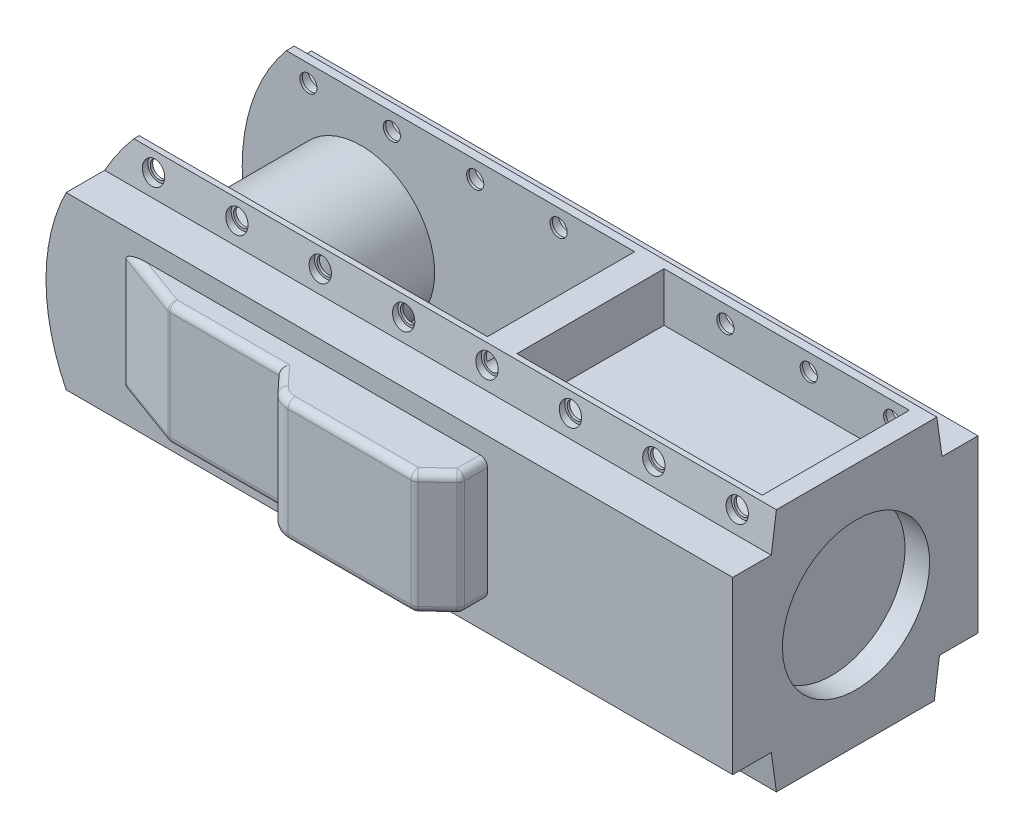
SolidWorks part; units mm, degrees
note: The reader was unsure of these and kept them because the rebuilt part matched: shared geometry of "Sketch8<3>".
ref_plane "Front Plane" through (0, 0, 0) normal (0, 0, 1) x (1, 0, 0)
ref_plane "Top Plane" through (0, 0, 0) normal (0, 1, 0) x (1, 0, 0)
ref_plane "Right Plane" through (0, 0, 0) normal (1, 0, 0) x (0, 0, -1)
sketch "Sketch1" plane through (0, 0, 0) normal (0, 0, 1) x (1, 0, 0)
sketch_block_instance "Block5-1"
sketch_block "Block5" parameters "D1"=43.5311
sketch "Sketch2" plane through (0, 0, 0) normal (0, 0, 1) x (1, 0, 0)
  line L0 (130.4545, 46.606) -> (113.6122, 46.606) construction
  line L1 (113.6075, 146.2711) -> (-166.3925, 146.2711)
  line L2 (113.6075, 146.2711) -> (113.6075, 46.606)
  line L3 (113.6075, 46.606) -> (-166.3925, 46.606)
  line L4 (-166.3925, 146.2711) -> (-166.3925, 46.606)
  dimension "D1" = 280
extrude "Boss-Extrude1" add sketch "Sketch2" along normal mid plane 100
sketch "Sketch3" plane through (0, 0, 50) normal (0, 0, 1) x (1, 0, 0)
  line L0 (113.6075, 146.2711) -> (-166.3925, 146.2711) construction
  line L1 (-166.3925, 46.606) -> (113.6075, 46.606) construction
  line L2 (-148.3925, 146.2711) -> (-166.3925, 146.2711)
  line L3 (-166.3925, 146.2711) -> (-166.3925, 46.606)
  line L4 (-166.3925, 46.606) -> (-148.3925, 46.606)
  arc A0 (-148.3925, 146.2711) -> (-148.3925, 46.606) centre (-88.4125, 96.4386) ccw
  line M4 (113.6075, 146.2711) -> (-166.3925, 146.2711)
  line M5 (-166.3925, 146.2711) -> (-166.3925, 46.606)
  line M6 (-166.3925, 46.606) -> (113.6075, 46.606)
  dimension "D1" = 18
  dimension "D2" = 18
extrude "Cut-Extrude1" cut sketch "Sketch3" against normal through all contours A0 M4 M5 | A0 L3 M6
sketch "Sketch4" plane through (0, 146.2711, 0) normal (0, 1, 0) x (1, 0, 0)
  line L0 (113.6075, 0) -> (-117.9126, 0) construction
  line L1 (113.6075, -50) -> (113.6075, 50) construction
  line L2 (-148.3925, 50) -> (-148.3925, -50) construction
  line L3 (-290.3925, 30) -> (-6.3925, 30)
  line L4 (-290.3925, 30) -> (-290.3925, -30)
  line L5 (-290.3925, -30) -> (-6.3925, -30)
  line L6 (-6.3925, 30) -> (-6.3925, -30)
  line L7 (-290.3925, 30) -> (-6.3925, -30) construction
  line L8 (-290.3925, -30) -> (-6.3925, 30) construction
  point P5 (-148.3925, 0)
  dimension "D2" = 120
  dimension "D3" = 60
extrude "Cut-Extrude2" cut sketch "Sketch4" against normal through all
sketch "Sketch6" plane through (113.6075, 0, 0) normal (1, 0, 0) x (0, 0, -1)
  line L1 (-50, 146.2711) -> (-35, 146.2711)
  line L2 (-50, 146.2711) -> (-50, 131.2711)
  line L3 (-50, 131.2711) -> (-35, 131.2711)
  line L4 (-35, 146.2711) -> (-35, 131.2711)
  line L5 (50, 146.2711) -> (36.0483, 146.2711)
  line L6 (50, 146.2711) -> (50, 131.2711)
  line L7 (50, 131.2711) -> (36.0483, 131.2711)
  line L8 (36.0483, 146.2711) -> (36.0483, 131.2711)
  line L9 (-50, 46.606) -> (-35, 46.606)
  line L10 (-50, 46.606) -> (-50, 61.606)
  line L11 (-50, 61.606) -> (-35, 61.606)
  line L12 (-35, 46.606) -> (-35, 61.606)
  line L13 (50, 46.606) -> (35, 46.606)
  line L14 (50, 46.606) -> (50, 61.606)
  line L15 (50, 61.606) -> (35, 61.606)
  line L16 (35, 46.606) -> (35, 61.606)
  dimension "D1" = 15
  dimension "D2" = 15
  dimension "D3" = 15
  dimension "D4" = 13.9517
  dimension "D5" = 15
  dimension "D6" = 15
  dimension "D7" = 15
  dimension "D8" = 15
extrude "Cut-Extrude3" cut sketch "Sketch6" against normal through all
sketch "Sketch7" plane through (0, 0, 0) normal (0, 0, 1) x (1, 0, 0)
  circle A0 centre (-117.9126, 98.0301) radius 30
  dimension "D1" = 60
extrude "Boss-Extrude2" add sketch "Sketch7" along normal mid plane 60
sketch "Sketch8" plane through (0, 0, 50) normal (0, 0, 1) x (1, 0, 0)
  line L0 (107.0874, 98.0301) -> (-117.9126, 98.0301) construction
  line L1 (-136.3925, 123.0301) -> (13.6075, 123.0301)
  line L2 (-136.3925, 123.0301) -> (-136.3925, 73.0301)
  line L3 (-136.3925, 73.0301) -> (13.6075, 73.0301)
  line L4 (13.6075, 123.0301) -> (13.6075, 73.0301)
  line L5 (-136.3925, 123.0301) -> (13.6075, 73.0301) construction
  line L6 (-136.3925, 73.0301) -> (13.6075, 123.0301) construction
  line L7 (113.6075, 61.606) -> (113.6075, 131.2711) construction
  line L9 (13.6075, 123.0301) -> (-61.3925, 123.0301)
  line L10 (13.6075, 123.0301) -> (13.6075, 73.0301)
  line L11 (13.6075, 73.0301) -> (-61.3925, 73.0301)
  line L12 (-61.3925, 123.0301) -> (-61.3925, 73.0301)
  point P0 (-61.3925, 98.0301)
  dimension "D1" = 50
  dimension "D2" = 150
  dimension "D3" = 100
extrude "Boss-Extrude3" add sketch "Sketch8" along normal blind 10 contours L12 L1 L2 L3 | L1 L12 L3 L4
extrude "Boss-Extrude4" add sketch "Sketch8<3>" along normal blind 20 contours L1 L12 L3 L4
sketch "Sketch8<3>" plane through (0, 0, 50) normal (0, 0, 1) x (1, 0, 0) same geometry as "Sketch8"
chamfer "Chamfer1" distance 10 angle 43 4 edges at (13.6075, 98.0301, 70) (-23.8925, 73.0301, 70) (-61.3925, 98.0301, 70) (-23.8925, 123.0301, 70)
chamfer "Chamfer2" distance 30 angle 20 1 edges at (-136.3925, 98.0301, 60)
fillet "Fillet1" radius 3 15 edges at (-120.1299, 73.0301, 55) (-120.1299, 123.0301, 55) (-83.8925, 73.0301, 60) (-83.8925, 123.0301, 60) (-106.3925, 98.0301, 60) (13.6075, 98.0301, 60.6748) (8.6075, 73.0301, 65.3374) (3.6075, 98.0301, 70) (8.6075, 123.0301, 65.3374) (13.6075, 123.0301, 55.3374) (13.6075, 73.0301, 55.3374) (-24.2299, 73.0301, 70) (-56.7299, 73.0301, 65) (-24.2299, 123.0301, 70) (-56.7299, 123.0301, 65)
sketch "Sketch10" plane through (0, 146.2711, 0) normal (0, 1, 0) x (1, 0, 0)
  line L0 (-6.3925, 30) -> (-148.3925, 30) construction
  line L1 (5.6075, 30) -> (105.6075, 30)
  line L2 (5.6075, 30) -> (5.6075, -30)
  line L3 (5.6075, -30) -> (105.6075, -30)
  line L4 (105.6075, 30) -> (105.6075, -30)
  line L5 (-148.3925, -30) -> (-6.3925, -30) construction
  line L6 (-6.3925, -30) -> (-6.3925, 30) construction
  dimension "D1" = 12
  dimension "D2" = 100
extrude "Cut-Extrude4" cut sketch "Sketch10" against normal blind 20
fillet "Fillet2" radius 10 3 edges at (-51.6853, 73.9088, 69.1213) (-51.6853, 122.1514, 69.1213) (-52.0673, 98.0301, 70)
chamfer "Chamfer3" distance 20 angle 8 4 edges at (-17.3925, 146.2711, 35) (-17.3925, 46.606, 35) (-17.3925, 46.606, -35) (-17.3925, 146.2711, -36.0483)
sketch "Sketch11" plane through (0, 0, 50) normal (0, 0, 1) x (1, 0, 0)
  line L0 (115.4482, 139.2711) -> (75.4482, 139.2711) construction
  line L1 (113.6075, 146.2711) -> (113.6075, 131.2711) construction
  line L2 (-148.3925, 146.2711) -> (113.6075, 146.2711) construction
  circle A0 centre (98.6075, 139.2711) radius 3.5
  dimension "D1" = 7
  dimension "D3" = 15
  dimension "D2" = 40
  dimension "D4" = 7
extrude "Cut-Extrude5" cut sketch "Sketch11" against normal blind 30
sketch "Sketch12" plane through (0, 0, 50) normal (0, 0, 1) x (1, 0, 0)
  circle A0 centre (98.6075, 139.2711) radius 4.5
  dimension "D1" = 9
extrude "Cut-Extrude6" cut sketch "Sketch12" against normal blind 19
pattern_linear "LPattern1" count 8 spacing 34 along (-1, 0, 0) of "Cut-Extrude5", "Cut-Extrude6"
ref_plane "Plane1" through (0, 96.4386, 0) normal (0, 1, 0) x (1, 0, 0)
mirror "Mirror1" about plane through (0, 96.4386, 0) normal (0, 1, 0) of "LPattern1", "Cut-Extrude5", "Cut-Extrude6"
ref_plane "Plane2" through (0, 0, 0) normal (0, 0, 1) x (1, 0, 0)
mirror "Mirror8" about plane through (0, 0, 0) normal (0, 0, 1) of "Mirror1", "Cut-Extrude5", "Cut-Extrude6", "LPattern1"
sketch "Sketch13" plane through (113.6075, 0, 0) normal (1, 0, 0) x (0, 0, -1)
  line L0 (0.5241, 146.2711) -> (0, 46.606) construction
  line L1 (-32.1892, 146.2711) -> (33.2374, 146.2711) construction
  line L2 (-32.1892, 46.606) -> (32.1892, 46.606) construction
  circle A0 centre (0.2621, 96.4386) radius 30
  dimension "D1" = 60
extrude "Cut-Extrude7" cut sketch "Sketch13" against normal blind 10
